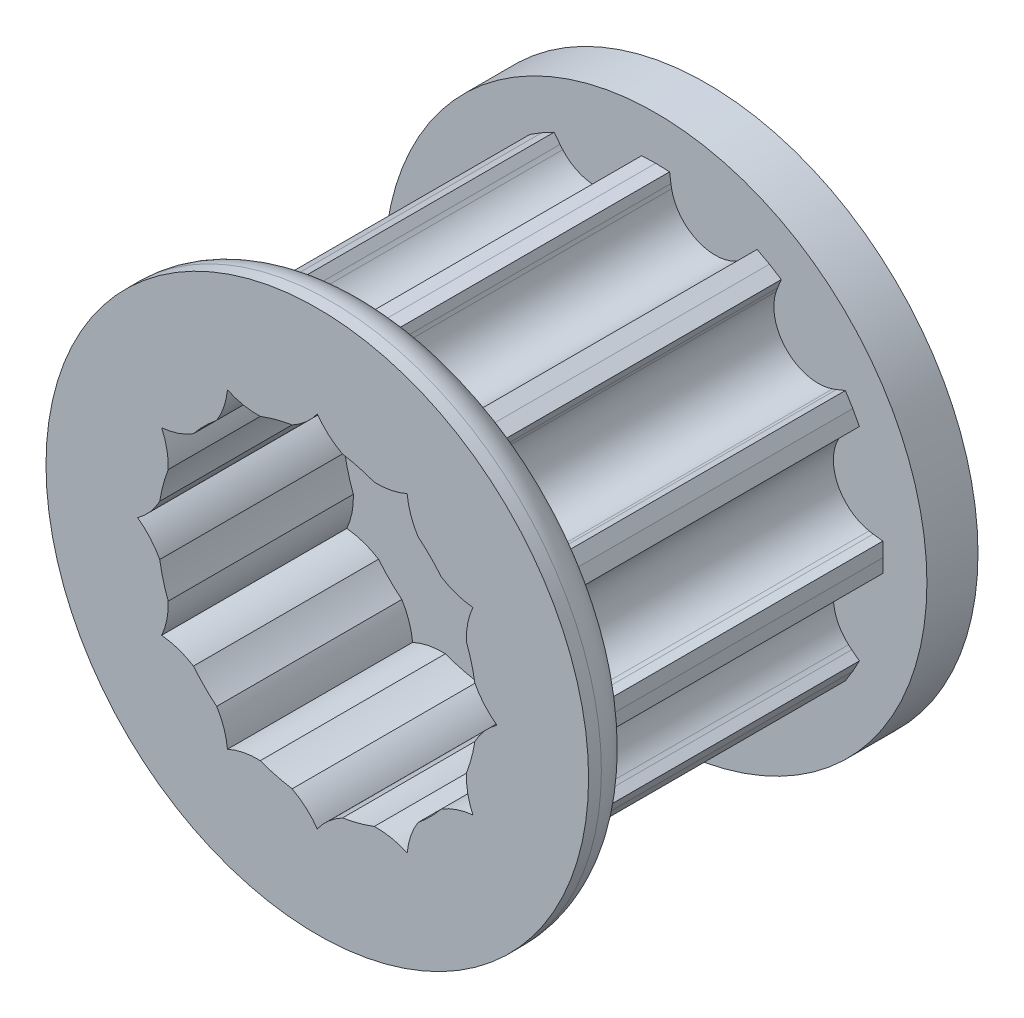
SolidWorks part; units mm, degrees
ref_plane "Face" through (0, 0, 0) normal (0, 0, 1) x (1, 0, 0)
ref_plane "Dessus" through (0, 0, 0) normal (0, 1, 0) x (1, 0, 0)
ref_plane "Droite" through (0, 0, 0) normal (1, 0, 0) x (0, 0, -1)
sketch "Esquisse1" plane through (0, 0, 0) normal (0, 0, 1) x (1, 0, 0)
  line L0 (0, 0) -> (-0.9886, 3.6896) construction
  line L1 (0, 0) -> (0.9886, 3.6896) construction
  line L2 (-1.1459, 4.2764) -> (-0.9886, 3.6896) construction
  line L3 (1.1459, 4.2764) -> (0.9886, 3.6896) construction
  line L4 (-1.3689, 3.566) -> (0, 0) construction
  line L5 (0, 0) -> (0, 4.4273) construction
  line L6 (-0.7525, 2.8082) -> (0, 0)
  line L7 (0, 0) -> (0.7525, 2.8082)
  line L8 (-0.2397, 3.4094) -> (-0.2189, 3.559)
  line L9 (-0.2189, 3.559) -> (0, 3.5657)
  line L10 (0.2397, 3.4094) -> (0.2189, 3.559)
  line L11 (0.2189, 3.559) -> (0, 3.5657)
  arc A0 (-0.9886, 3.6896) -> (0.9886, 3.6896) centre (0, 0) cw construction
  arc A1 (1.1459, 4.2764) -> (-1.1459, 4.2764) centre (0, 0) ccw construction
  arc A2 (0.9229, 3.4442) -> (-0.9229, 3.4442) centre (0, 0) ccw construction
  arc A3 (-0.9886, 3.6896) -> (-1.3689, 3.566) centre (0, 0) ccw construction
  arc A4 (-0.9229, 3.4442) -> (-1.2778, 3.3289) centre (0, 0) ccw construction
  arc A5 (-0.7887, 2.9435) -> (-0.3879, 3.3717) centre (-0.9323, 3.4796) ccw construction
  arc A6 (-0.3879, 3.3717) -> (-0.3784, 3.4286) centre (-1.3689, 3.566) ccw construction
  arc A7 (0.9323, 3.4796) -> (-0.9323, 3.4796) centre (0, 0) ccw construction
  arc A8 (-0.3784, 3.4286) -> (-0.2399, 3.5576) centre (-0.2298, 3.408) cw construction
  arc A9 (-0.2399, 3.5576) -> (0.2399, 3.5576) centre (0, 0) cw construction
  arc A10 (0.3784, 3.4286) -> (0.2399, 3.5576) centre (0.2298, 3.408) ccw construction
  arc A11 (0.3879, 3.3717) -> (0.3784, 3.4286) centre (1.3689, 3.566) cw construction
  arc A12 (0.7887, 2.9435) -> (0.3879, 3.3717) centre (0.9323, 3.4796) cw construction
  arc A13 (-0.7525, 2.8082) -> (-0.2506, 3.3445) centre (-0.9323, 3.4796) ccw
  arc A14 (-0.2506, 3.3445) -> (-0.2397, 3.4094) centre (-1.3689, 3.566) ccw
  arc A15 (-0.2397, 3.4094) -> (-0.2304, 3.418) centre (-0.2298, 3.408) cw construction
  arc A16 (-0.2304, 3.418) -> (0.2304, 3.418) centre (0, 0) cw construction
  arc A17 (0.2397, 3.4094) -> (0.2304, 3.418) centre (0.2298, 3.408) ccw construction
  arc A18 (0.2506, 3.3445) -> (0.2397, 3.4094) centre (1.3689, 3.566) cw
  arc A19 (0.7525, 2.8082) -> (0.2506, 3.3445) centre (0.9323, 3.4796) cw
  dimension "D2" = 0.254
  dimension "D3" = 0.555
  dimension "D4" = 2
  dimension "D5" = 0.4
  dimension "D6" = 1.38
  dimension "D7" = 0.15
  dimension "D8" = 1
  dimension "D9" = 0.14
  dimension "D1" = 30
extrude "Boss.-Extru.1" add sketch "Esquisse1" along normal mid plane 4.5
pattern_circular "Répétition circulaire2" count 12 over 360 about axis through (0, 0, 2.25) along (0, 0, -1) of "Boss.-Extru.1"
sketch "Sketch3" plane through (0, 0, 0) normal (0, 0, 1) x (1, 0, 0)
  circle A0 centre (0, 0) radius 4.25
  dimension "D1" = 8.5
extrude "Boss-Extrude1" add sketch "Sketch3" along normal blind 0.8 from surface starting at face at (0, 0, 2.25)
mirror "Mirror2" about plane through (0, 0, 0) normal (0, 0, 1) of "Boss-Extrude1"
sketch "Esquisse2" plane through (0, 0, 3.05) normal (0, 0, 1) x (1, 0, 0)
  circle A0 centre (0, 0) radius 5 construction
  circle A1 centre (0, 0) radius 2.5
  circle A2 centre (0, 0) radius 1.1
  dimension "D1" = 5
  dimension "D2" = 10
  dimension "D3" = 2.2
extrude "Enlèv. mat.-Extru.1" cut sketch "Esquisse2" against normal blind 2.9 contours A1
extrude "Cut-Extrude1" cut sketch "Esquisse2<3>" against normal blind 10 contours A2
sketch "Esquisse2<3>" plane through (0, 0, 3.05) normal (0, 0, 1) x (1, 0, 0) same geometry as "Esquisse2"
fillet "Fillet1" radius 0.6 1 edges at (-4.25, 0, 2.25)
sketch "Sketch4" plane through (0, 0, 3.05) normal (0, 0, 1) x (1, 0, 0)
  arc A73 (-2.4378, -1.4075) -> (-2.8149, 0) centre (-3.4796, -0.9323) ccw
  arc A74 (-1.4075, -2.4378) -> (-2.4378, -1.4075) centre (-2.5472, -2.5472) ccw
  arc A75 (0, -2.8149) -> (-1.4075, -2.4378) centre (-0.9323, -3.4796) ccw
  arc A76 (1.4075, -2.4378) -> (0, -2.8149) centre (0.9323, -3.4796) ccw
  arc A77 (2.4378, -1.4075) -> (1.4075, -2.4378) centre (2.5472, -2.5472) ccw
  arc A78 (2.8149, 0) -> (2.4378, -1.4075) centre (3.4796, -0.9323) ccw
  arc A79 (2.4378, 1.4075) -> (2.8149, 0) centre (3.4796, 0.9323) ccw
  arc A80 (1.4075, 2.4378) -> (2.4378, 1.4075) centre (2.5472, 2.5472) ccw
  arc A81 (0, 2.8149) -> (1.4075, 2.4378) centre (0.9323, 3.4796) ccw
  arc A82 (-1.4075, 2.4378) -> (0, 2.8149) centre (-0.9323, 3.4796) ccw
  arc A83 (-2.4378, 1.4075) -> (-1.4075, 2.4378) centre (-2.5472, 2.5472) ccw
  arc A84 (-2.8149, 0) -> (-2.4378, 1.4075) centre (-3.4796, 0.9323) ccw
  arc A85 (-2.4378, -1.4075) -> (-2.8149, 0) centre (-3.4796, -0.9323) ccw
  arc A86 (-1.4075, -2.4378) -> (-2.4378, -1.4075) centre (-2.5472, -2.5472) ccw
  arc A87 (0, -2.8149) -> (-1.4075, -2.4378) centre (-0.9323, -3.4796) ccw
  arc A88 (1.4075, -2.4378) -> (0, -2.8149) centre (0.9323, -3.4796) ccw
  arc A89 (2.4378, -1.4075) -> (1.4075, -2.4378) centre (2.5472, -2.5472) ccw
  arc A90 (2.8149, 0) -> (2.4378, -1.4075) centre (3.4796, -0.9323) ccw
  arc A91 (2.4378, 1.4075) -> (2.8149, 0) centre (3.4796, 0.9323) ccw
  arc A92 (1.4075, 2.4378) -> (2.4378, 1.4075) centre (2.5472, 2.5472) ccw
  arc A93 (0, 2.8149) -> (1.4075, 2.4378) centre (0.9323, 3.4796) ccw
  arc A94 (-1.4075, 2.4378) -> (0, 2.8149) centre (-0.9323, 3.4796) ccw
  arc A95 (-2.4378, 1.4075) -> (-1.4075, 2.4378) centre (-2.5472, 2.5472) ccw
  arc A96 (-2.8149, 0) -> (-2.4378, 1.4075) centre (-3.4796, 0.9323) ccw
  dimension "D1" = 0.45
extrude "Cut-Extrude2" cut sketch "Sketch4" against normal up to surface (2.9 mm away) up to face at (1.1, 0, 0.15)
